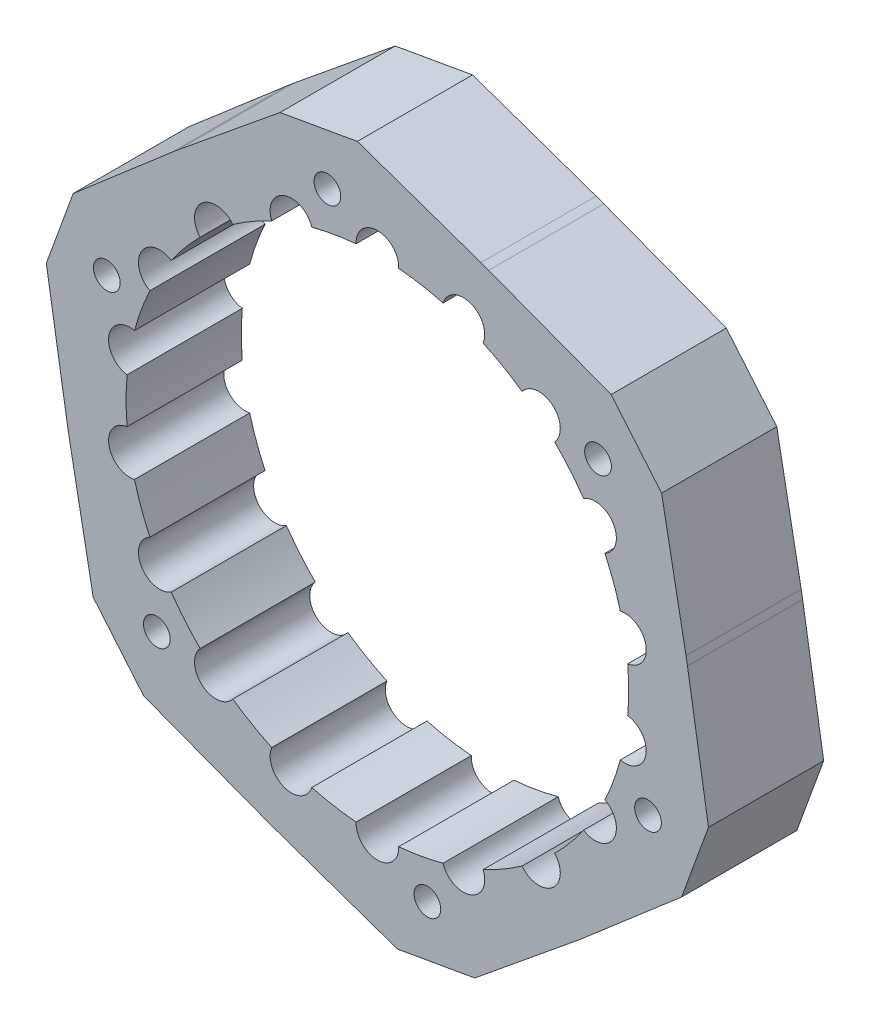
SolidWorks part; units mm, degrees
ref_plane "Front Plane" through (0, 0, 0) normal (0, 0, 1) x (1, 0, 0)
ref_plane "Top Plane" through (0, 0, 0) normal (0, 1, 0) x (1, 0, 0)
ref_plane "Right Plane" through (0, 0, 0) normal (1, 0, 0) x (0, 0, -1)
sketch "Sketch1" plane through (0, 0, 0) normal (0, 0, 1) x (1, 0, 0)
  line L0 (-16.417, 45.1052) -> (0, 0) construction
  line L1 (0, 0) -> (-8.3351, 47.2708) construction
  circle A2 centre (0, 0) radius 60
  arc A36 (-12.532, 46.3352) -> (-20.1836, 43.5502) centre (-16.417, 45.1052) ccw
  arc A42 (-4.0713, 47.827) -> (-12.532, 46.3352) centre (0, 0) ccw
  circle A60 centre (0, 0) radius 48 construction
  arc A61 (4.0713, 47.827) -> (-4.0713, 47.827) centre (0, 48) ccw
  arc A62 (12.532, 46.3352) -> (4.0713, 47.827) centre (0, 0) ccw
  arc A63 (20.1836, 43.5502) -> (12.532, 46.3352) centre (16.417, 45.1052) ccw
  arc A64 (27.6238, 39.2546) -> (20.1836, 43.5502) centre (0, 0) ccw
  arc A65 (33.8614, 34.0206) -> (27.6238, 39.2546) centre (30.8538, 36.7701) ccw
  arc A66 (39.3838, 27.4394) -> (33.8614, 34.0206) centre (0, 0) ccw
  arc A67 (43.4551, 20.3876) -> (39.3838, 27.4394) centre (41.5692, 24) ccw
  arc A68 (46.3934, 12.3146) -> (43.4551, 20.3876) centre (0, 0) ccw
  arc A69 (47.8074, 4.2956) -> (46.3934, 12.3146) centre (47.2708, 8.3351) ccw
  arc A70 (47.8074, -4.2956) -> (47.8074, 4.2956) centre (0, 0) ccw
  arc A71 (46.3934, -12.3146) -> (47.8074, -4.2956) centre (47.2708, -8.3351) ccw
  arc A72 (43.4551, -20.3876) -> (46.3934, -12.3146) centre (0, 0) ccw
  arc A73 (39.3838, -27.4394) -> (43.4551, -20.3876) centre (41.5692, -24) ccw
  arc A74 (33.8614, -34.0206) -> (39.3838, -27.4394) centre (0, 0) ccw
  arc A75 (27.6238, -39.2546) -> (33.8614, -34.0206) centre (30.8538, -36.7701) ccw
  arc A76 (20.1836, -43.5502) -> (27.6238, -39.2546) centre (0, 0) ccw
  arc A77 (12.532, -46.3352) -> (20.1836, -43.5502) centre (16.417, -45.1052) ccw
  arc A78 (4.0713, -47.827) -> (12.532, -46.3352) centre (0, 0) ccw
  arc A79 (-4.0713, -47.827) -> (4.0713, -47.827) centre (0, -48) ccw
  arc A80 (-12.532, -46.3352) -> (-4.0713, -47.827) centre (0, 0) ccw
  arc A81 (-20.1836, -43.5502) -> (-12.532, -46.3352) centre (-16.417, -45.1052) ccw
  arc A82 (-27.6238, -39.2546) -> (-20.1836, -43.5502) centre (0, 0) ccw
  arc A83 (-33.8614, -34.0206) -> (-27.6238, -39.2546) centre (-30.8538, -36.7701) ccw
  arc A84 (-39.3838, -27.4394) -> (-33.8614, -34.0206) centre (0, 0) ccw
  arc A85 (-43.4551, -20.3876) -> (-39.3838, -27.4394) centre (-41.5692, -24) ccw
  arc A86 (-46.3934, -12.3146) -> (-43.4551, -20.3876) centre (0, 0) ccw
  arc A87 (-47.8074, -4.2956) -> (-46.3934, -12.3146) centre (-47.2708, -8.3351) ccw
  arc A88 (-47.8074, 4.2956) -> (-47.8074, -4.2956) centre (0, 0) ccw
  arc A89 (-46.3934, 12.3146) -> (-47.8074, 4.2956) centre (-47.2708, 8.3351) ccw
  arc A90 (-43.4551, 20.3876) -> (-46.3934, 12.3146) centre (0, 0) ccw
  arc A91 (-39.3838, 27.4394) -> (-43.4551, 20.3876) centre (-41.5692, 24) ccw
  arc A92 (-33.8614, 34.0206) -> (-39.3838, 27.4394) centre (0, 0) ccw
  arc A93 (-27.6238, 39.2546) -> (-33.8614, 34.0206) centre (-30.8538, 36.7701) ccw
  arc A94 (-20.1836, 43.5502) -> (-27.6238, 39.2546) centre (0, 0) ccw
  point P1 (-20.4295, 43.4354)
  point P59 (0, 0)
  point P85 (0, 0)
  dimension "D1" = 4.075
  dimension "D2" = 48
  dimension "D3" = 120
  dimension "D5" = 18
  dimension "D4" = 10
extrude "Boss-Extrude1" add sketch "Sketch1" along normal blind 22
sketch "Sketch2" plane through (0, 0, 22) normal (0, 0, 1) x (1, 0, 0)
  line L0 (0, 0) -> (0, 60) construction
  line L1 (0, 0) -> (-9.5506, 54.1644) construction
  circle A0 centre (0, 0) radius 55 construction
  circle A1 centre (-9.5506, 54.1644) radius 2.55
  circle A2 centre (0, 0) radius 60 construction
  circle A3 centre (42.1324, 35.3533) radius 2.55
  circle A4 centre (51.6831, -18.8111) radius 2.55
  circle A5 centre (9.5506, -54.1644) radius 2.55
  circle A6 centre (-42.1324, -35.3533) radius 2.55
  circle A7 centre (-51.6831, 18.8111) radius 2.55
  point P5 (0, 0)
  point P22 (0, 0)
  dimension "D1" = 110
  dimension "D2" = 5.1
  dimension "D3" = 10
  dimension "D4" = 6
extrude "Cut-Extrude2" cut sketch "Sketch2" against normal through all
sketch "Sketch3" plane through (0, 0, 22) normal (0, 0, 1) x (1, 0, 0)
  line L0 (0, 0) -> (-9.5506, 54.1644) construction
  line L1 (-9.5506, 54.1644) -> (-11.2871, 64.0125) construction
  line L2 (0, 65) -> (0, 0) construction
  line L3 (-37.9588, 46.4664) -> (-18.5978, 62.2826)
  line L4 (-18.5978, 62.2826) -> (-3.8257, 64.8873)
  line L5 (-3.8257, 64.8873) -> (19.7772, 56.6468)
  line L6 (54.2812, 35.7568) -> (58.9462, 11.1959)
  line L7 (44.6394, 47.2475) -> (54.2812, 35.7568)
  line L8 (21.2617, 56.1065) -> (44.6394, 47.2475)
  line L9 (58.1069, -29.1305) -> (39.169, -45.4509)
  line L10 (63.2372, -15.0351) -> (58.1069, -29.1305)
  line L11 (59.2205, 9.6401) -> (63.2372, -15.0351)
  line L12 (3.8257, -64.8873) -> (-19.7772, -56.6468)
  line L13 (18.5978, -62.2826) -> (3.8257, -64.8873)
  line L14 (37.9588, -46.4664) -> (18.5978, -62.2826)
  line L15 (-54.2812, -35.7568) -> (-58.9462, -11.1959)
  line L16 (-44.6394, -47.2475) -> (-54.2812, -35.7568)
  line L17 (-21.2617, -56.1065) -> (-44.6394, -47.2475)
  line L18 (-58.1069, 29.1305) -> (-39.169, 45.4509)
  line L19 (-63.2372, 15.0351) -> (-58.1069, 29.1305)
  line L20 (-59.2205, -9.6401) -> (-63.2372, 15.0351)
  circle A0 centre (0, 0) radius 65 construction
  circle A1 centre (0, 0) radius 60 construction
  arc A2 (-37.9588, 46.4664) -> (19.7772, 56.6468) centre (0, 0) cw
  arc A3 (21.2617, 56.1065) -> (58.9462, 11.1959) centre (0, 0) cw
  arc A4 (59.2205, 9.6401) -> (39.169, -45.4509) centre (0, 0) cw
  arc A5 (37.9588, -46.4664) -> (-19.7772, -56.6468) centre (0, 0) cw
  arc A6 (-21.2617, -56.1065) -> (-58.9462, -11.1959) centre (0, 0) cw
  arc A7 (-59.2205, -9.6401) -> (-39.169, 45.4509) centre (0, 0) cw
  point P11 (-11.2117, 63.585)
  point P38 (0, 0)
  dimension "D1" = 130
  dimension "D2" = 15
  dimension "D3" = 6
extrude "Boss-Extrude2" add sketch "Sketch3" against normal blind 22
